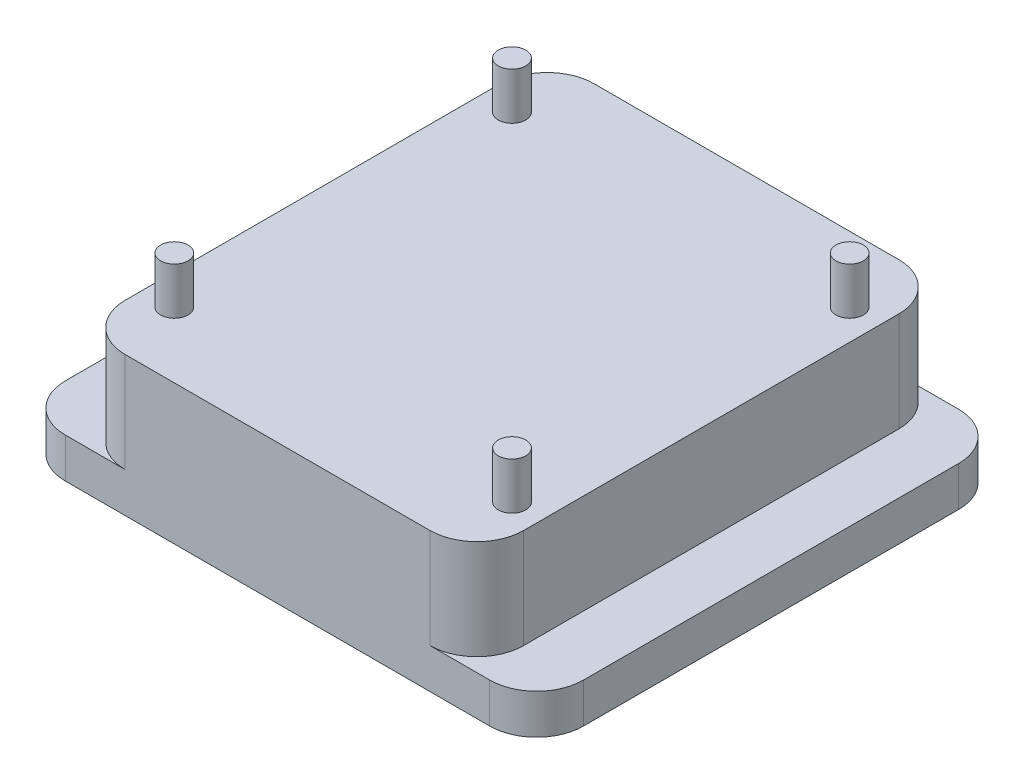
SolidWorks part; units mm, degrees
ref_plane "Front Plane" through (0, 0, 0) normal (0, 0, 1) x (1, 0, 0)
ref_plane "Top Plane" through (0, 0, 0) normal (0, 1, 0) x (1, 0, 0)
ref_plane "Right Plane" through (0, 0, 0) normal (1, 0, 0) x (0, 0, -1)
sketch "Sketch1" plane through (0, 0, 0) normal (0, 0, 1) x (1, 0, 0)
  line L1 (-28.067, -2.159) -> (28.067, -2.159)
  line L2 (-28.067, -2.159) -> (-28.067, 2.159)
  line L3 (-28.067, 2.159) -> (28.067, 2.159)
  line L4 (28.067, -2.159) -> (28.067, 2.159)
  line L5 (-28.067, -2.159) -> (28.067, 2.159) construction
  line L6 (-28.067, 2.159) -> (28.067, -2.159) construction
  line L7 (-21.59, 2.159) -> (21.59, 2.159)
  line L8 (-21.59, 2.159) -> (-21.59, 5.334)
  line L9 (-21.59, 5.334) -> (21.59, 5.334)
  line L10 (21.59, 2.159) -> (21.59, 5.334)
  line L11 (-21.59, 5.334) -> (21.59, 5.334)
  line L12 (-21.59, 5.334) -> (-21.59, 12.954)
  line L13 (-21.59, 12.954) -> (21.59, 12.954)
  line L14 (21.59, 5.334) -> (21.59, 12.954)
  point P0 (0, 0)
  point P10 (0, 5.334)
  point P11 (0, 12.954)
  dimension "D1" = 56.134
  dimension "D2" = 4.318
  dimension "D3" = 43.18
  dimension "D4" = 3.175
  dimension "D5" = 43.18
  dimension "D6" = 7.62
extrude "Boss-Extrude1" add sketch "Sketch1" along normal blind 50.8 contours L11 L14 L13 L12 L9 | L3 L10 L9 L8 | L1 L4 L3 L2 region at (0, 0, 0) region at (0, 3.7465, 0) region at (0, 9.144, 0)
sketch "Sketch2" plane through (0, 12.954, 0) normal (0, 1, 0) x (1, 0, 0)
  line L0 (-21.59, -50.8) -> (-21.59, 0) construction
  line L1 (-18.288, -7.112) -> (18.288, -7.112) construction
  line L2 (-18.288, -7.112) -> (-18.288, -43.688) construction
  line L3 (-18.288, -43.688) -> (18.288, -43.688) construction
  line L4 (18.288, -7.112) -> (18.288, -43.688) construction
  line L5 (-21.59, 0) -> (21.59, 0) construction
  circle A0 centre (-18.288, -7.112) radius 1.4859
  circle A1 centre (18.288, -7.112) radius 1.4859
  circle A2 centre (18.288, -43.688) radius 1.4859
  circle A3 centre (-18.288, -43.688) radius 1.4859
  point P4 (-18.288, -25.4)
  point P5 (-21.59, -25.4)
  point P6 (0, 0)
  point P10 (0, -7.112)
  dimension "D3" = 2.9718
  dimension "D4" = 2.9718
  dimension "D5" = 2.9718
  dimension "D6" = 2.9718
  dimension "D1" = 36.576
  dimension "D2" = 36.576
extrude "Boss-Extrude2" add sketch "Sketch2" along normal blind 5.08
fillet "Fillet1" radius 5.08 4 edges at (-21.59, 7.5565, 0) (21.59, 7.5565, 0) (21.59, 7.5565, 50.8) (-21.59, 7.5565, 50.8)
fillet "Fillet2" radius 5.08 4 edges at (-28.067, 0, 50.8) (-28.067, 0, 0) (28.067, 0, 50.8) (28.067, 0, 0)
